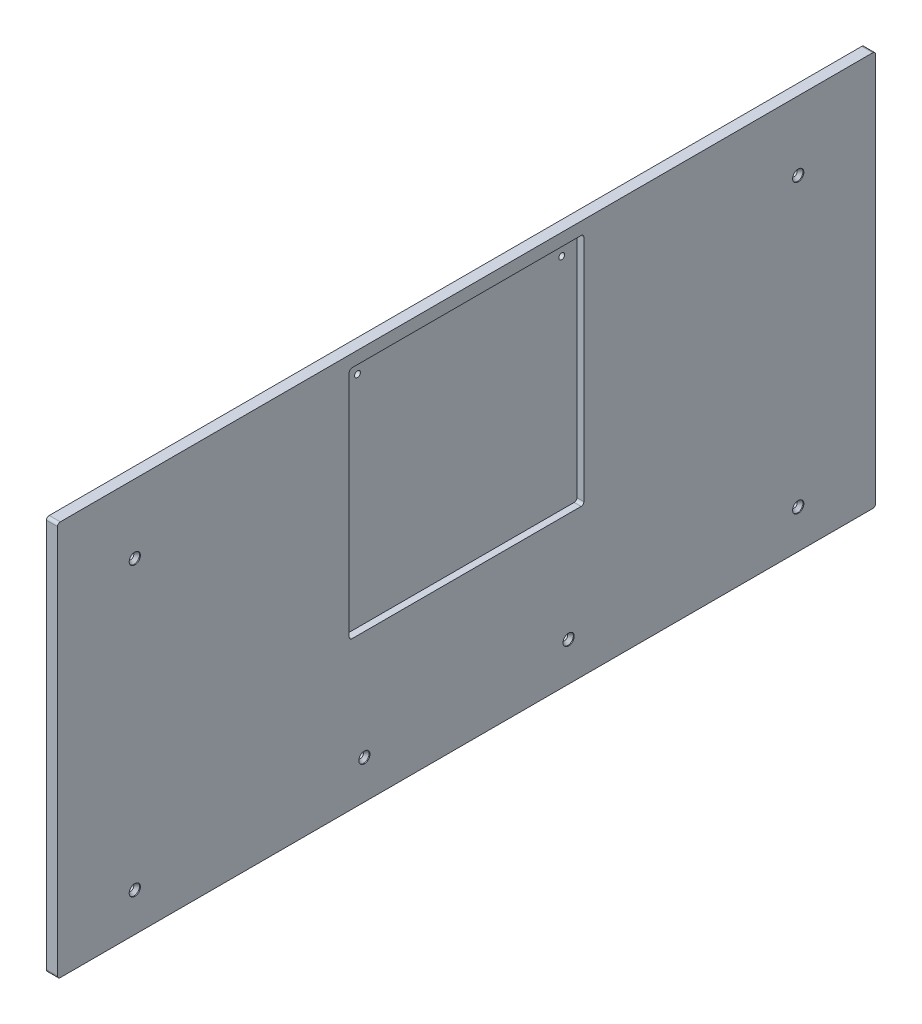
SolidWorks part; units mm, degrees
material "PE High Density"
ref_plane "Front Plane" through (0, 0, 0) normal (0, 0, 1) x (1, 0, 0)
ref_plane "Top Plane" through (0, 0, 0) normal (0, 1, 0) x (1, 0, 0)
ref_plane "Right Plane" through (0, 0, 0) normal (1, 0, 0) x (0, 0, -1)
sketch "Sketch1" plane through (0, 0, 0) normal (1, 0, 0) x (0, 0, -1)
  line L1 (0, 0) -> (940.882, 0)
  line L2 (0, 0) -> (0, 454.025)
  line L3 (0, 454.025) -> (940.882, 454.025)
  line L4 (940.882, 0) -> (940.882, 454.025)
  circle A8 centre (352.966, 422.275) radius 3.3734
  circle A9 centre (587.916, 422.275) radius 3.3734
  dimension "D4" = 6.7469
  dimension "D5" = 352.966
  dimension "D1" = 454.025
  dimension "D2" = 940.882
  dimension "D3" = 352.966
  dimension "D10" = 31.75
extrude "Boss-Extrude1" add sketch "Sketch1" along normal blind 12.7
fillet "Fillet1" radius 3.175 4 edges at (6.35, 454.025, -940.882) (6.35, 0, -940.882) (6.35, 0, 0) (6.35, 454.025, 0)
sketch "Sketch2" plane through (12.7, 0, 0) normal (1, 0, 0) x (0, 0, -1)
  line L0 (937.707, 454.025) -> (3.175, 454.025) construction
  line L1 (335.5035, 439.7375) -> (605.3785, 439.7375)
  line L2 (335.5035, 439.7375) -> (335.5035, 169.8625)
  line L3 (335.5035, 169.8625) -> (605.3785, 169.8625)
  line L4 (605.3785, 439.7375) -> (605.3785, 169.8625)
  circle A0 centre (352.966, 422.275) radius 3.3734 construction
  point P6 (470.441, 454.025)
  point P7 (470.441, 439.7375)
  dimension "D1" = 269.875
  dimension "D2" = 269.875
  dimension "D3" = 17.4625
extrude "Cut-Extrude1" cut sketch "Sketch2" against normal blind 7.9375
fillet "Fillet2" radius 3.175 4 edges at (8.7312, 439.7375, -335.5035) (8.7312, 439.7375, -605.3785) (8.7312, 169.8625, -335.5035) (8.7312, 169.8625, -605.3785)
hole_wizard "CSK for 1/4 Flat Head Machine Screw1" positions "Sketch4" profile "Sketch5" countersink size "1/4" standard "ANSI Inch" end condition through all
sketch "Sketch4" plane through (12.7, 0, 0) normal (1, 0, 0) x (0, 0, -1)
  line L0 (0, 450.85) -> (0, 3.175) construction
  line L2 (3.175, 0) -> (937.707, 0) construction
  line L3 (940.882, 3.175) -> (940.882, 450.85) construction
  point P0 (88.9, 374.65)
  point P2 (851.982, 374.65)
  point P4 (88.9, 44.45)
  point P6 (352.966, 44.45)
  point P8 (587.916, 44.45)
  point P10 (851.982, 44.45)
  point P15 (820.4932, 370.2615)
  point P16 (0, 0)
  point P17 (0, 0)
  point P18 (0, 0)
  point P19 (0, 0)
  point P20 (0, 0)
  point P27 (0, 0)
  dimension "D1" = 88.9
  dimension "D2" = 330.2
  dimension "D3" = 44.45
  dimension "D4" = 264.066
  dimension "D5" = 264.066
  dimension "D6" = 88.9
sketch "Sketch5" plane through (12.7, 374.65, -88.9) normal (0, 1, 0) x (0, 0, -1)
  line L0 (0, 0) -> (0, 12.7)
  line L1 (0, 12.7) -> (3.3782, 12.7)
  line L2 (3.3782, 12.7) -> (3.3782, 4.5369)
  line L3 (3.3782, 4.5369) -> (6.4389, 1.016)
  line L4 (6.4389, 1.016) -> (6.4389, 0)
  line L6 (6.4389, 0) -> (0, 0)
  line L7 (-3.3782, 4.5369) -> (-6.4389, 1.016) construction
  line L11 (0, -6.35) -> (0, 107.95) construction
  dimension "Thru Hole Dia." = 6.7564
  dimension "Thru Hole Depth" = 12.7
  dimension "C'Sink Dia." = 12.8778
  dimension "C'Sink Angle" = 82
  dimension "Head Clearance" = 1.016
